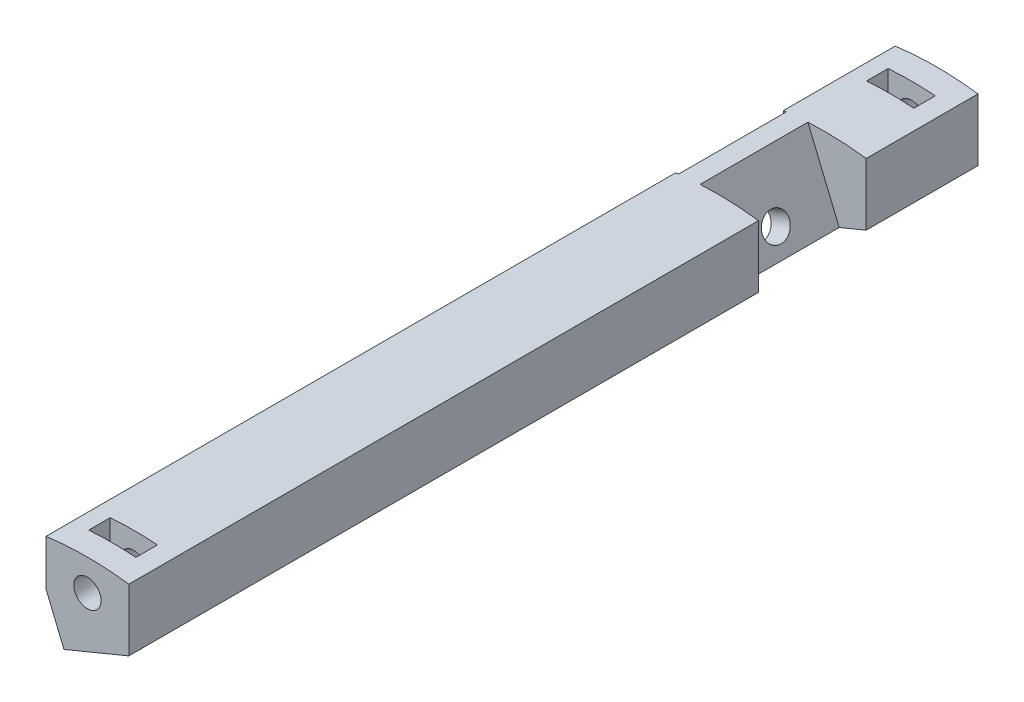
SolidWorks part; units mm, degrees
ref_plane "Plan de face" through (0, 0, 0) normal (0, 0, 1) x (1, 0, 0)
ref_plane "Plan de dessus" through (0, 0, 0) normal (0, 1, 0) x (1, 0, 0)
ref_plane "Plan de droite" through (0, 0, 0) normal (1, 0, 0) x (0, 0, -1)
sketch "Esquisse3" plane through (0, 0, 0) normal (0, 0, 1) x (1, 0, 0)
  line L3 (-5, 37.1652) -> (5, 37.1652) construction
  line L4 (-5, 37.1652) -> (-5, 0) construction
  line L5 (-5, 0) -> (5, 0) construction
  line L6 (5, 37.1652) -> (5, 0) construction
  line L7 (8.9994, 41.4168) -> (9.1038, 41.3823)
  line L8 (0, 0) -> (0, 37.5) construction
  line L9 (0, 0) -> (-14.3506, 34.6455) construction
  line L21 (15.6441, 34.081) -> (35.1609, -13.0369) construction
  line L30 (15.6441, 34.081) -> (-2.8335, 26.4273) construction
  line L31 (35.1609, -13.0369) -> (16.6833, -20.6905) construction
  line L32 (-2.8335, 26.4273) -> (16.6833, -20.6905) construction
  line L33 (-2.8335, 26.4273) -> (-10.4872, 44.9049) construction
  line L34 (-2.8335, 26.4273) -> (-0.9858, 27.1927) construction
  line L35 (-10.4872, 44.9049) -> (-8.6394, 45.6703) construction
  line L36 (-0.9858, 27.1927) -> (-8.6394, 45.6703) construction
  line L38 (5, 29.6657) -> (-2.8335, 26.4273)
  line L39 (-2.8335, 26.4273) -> (-5, 31.6576)
  line L40 (-5, 31.6576) -> (-5, 37.1652)
  line L41 (5, 37.1652) -> (5, 29.6657)
  circle A0 centre (0, 0) radius 37.5 construction
  circle A1 centre (0, 0) radius 30 construction
  arc A2 (-5, 37.1652) -> (5, 37.1652) centre (0, 0) cw
  point P5 (0, 0)
  dimension "D1" = 75
  dimension "D2" = 60
  dimension "D4" = 22.5
  dimension "D5" = 51
  dimension "D3" = 10
  dimension "D6" = 20
  dimension "D7" = 20
  dimension "D8" = 2
extrude "Boss.-Extru.2" add sketch "Esquisse3" along normal blind 102.5
sketch "Esquisse8" plane through (0, 0, 0) normal (0, 0, -1) x (-1, 0, 0)
  line L0 (-30, 0) -> (-37.5, 0) construction
  circle A0 centre (0, 0) radius 33.75 construction
  circle A1 centre (0, 33.75) radius 1.75
  circle A2 centre (0, 0) radius 37.5 construction
  circle A3 centre (0, 0) radius 30 construction
  point P10 (-33.75, 0)
  dimension "D2" = 3.5
  dimension "D3" = 60
extrude "Enlèv. mat.-Extru.5" cut sketch "Esquisse8" against normal blind 11.5
sketch "Esquisse9" plane through (0, 0, 0) normal (0, 0, -1) x (-1, 0, 0)
  line L0 (-2.85, 37.3915) -> (-2.85, 31.9954)
  line L1 (-2.85, 31.9954) -> (0, 30.35)
  line L2 (0, 30.35) -> (2.85, 31.9954)
  line L3 (2.85, 31.9954) -> (2.85, 37.3915)
  line L4 (-2.85, 31.9954) -> (2.85, 31.9954) construction
  arc A0 (5, 37.1652) -> (-5, 37.1652) centre (0, 0) ccw construction
  arc A1 (2.85, 37.3915) -> (-2.85, 37.3915) centre (0, 0) ccw
  circle A2 centre (0, 33.75) radius 1.75 construction
  point P9 (0, 31.9954)
  dimension "D3" = 3.4
  dimension "D1" = 120
  dimension "D2" = 5.7
extrude "Enlèv. mat.-Extru.6" cut sketch "Esquisse9" against normal blind 2.6 from offset 3 offset against normal yes
sketch "Esquisse14" plane through (0, 0, 102.5) normal (0, 0, 1) x (1, 0, 0)
  line L13 (16.2561, 33.7933) -> (35.3903, -12.4007) construction
  line L15 (35.3903, -12.4007) -> (16.9127, -20.0543) construction
  line L16 (-2.2215, 26.1396) -> (16.9127, -20.0543) construction
  line L17 (0, 0) -> (-37.5, 0) construction
  line L18 (0, 0) -> (-14.3506, 34.6455) construction
  line L26 (16.2561, 33.7933) -> (-2.2215, 26.1396) construction
  line L27 (-2.2215, 26.1396) -> (-9.8751, 44.6172) construction
  line L28 (-9.8751, 44.6172) -> (-8.0274, 45.3826) construction
  line L29 (-8.0274, 45.3826) -> (-0.3737, 26.905) construction
  line L36 (-0.5644, 27.3654) -> (1.7458, 28.3209)
  line L37 (5, 29.6657) -> (-2.8335, 26.4273) construction
  line L38 (1.7458, 28.3209) -> (-2.0335, 37.4448)
  line L40 (-0.5644, 27.3654) -> (-4.6428, 37.2115)
  circle A0 centre (0, 0) radius 37.5 construction
  arc A1 (5, 37.1652) -> (-5, 37.1652) centre (0, 0) ccw construction
  arc A3 (-2.0335, 37.4448) -> (-4.6428, 37.2115) centre (0, 0) ccw
  dimension "D1" = 2
  dimension "D2" = 20
  dimension "D3" = 67.5
  dimension "D4" = 2.5
  dimension "D6" = 50
  dimension "D7" = 20
extrude "Enlèv. mat.-Extru.11" cut sketch "Esquisse14" against normal blind 13 from offset 76 offset against normal yes
sketch "Esquisse15" plane through (11.5031, 4.7647, 0) normal (0.9239, 0.3827, 0) x (0, 0, -1)
  line L0 (-13.5, 25.4965) -> (-102.5, 25.4965) construction
  line L2 (-20, 28.4965) -> (-13.5, 28.4965) construction
  line L3 (-13.5, 25.497) -> (-13.5, 35.3727) construction
  line L4 (-20, 28.4965) -> (-26.5, 28.4965) construction
  line L5 (-26.5, 25.497) -> (-26.5, 35.3727) construction
  circle A0 centre (-20, 28.4965) radius 1.625
  dimension "D1" = 3.25
  dimension "D3" = 3
extrude "Enlèv. mat.-Extru.12" cut sketch "Esquisse15" against normal through all
chamfer "Chanfrein1" distance 2.5 angle 45 2 edges at (-1.699, 26.8963, 13.5) (-1.699, 26.8963, 26.5)
sketch "Esquisse16" plane through (0, 0, 102.5) normal (0, 0, 1) x (1, 0, 0)
  line L0 (-37.5, 0) -> (-30, 0) construction
  circle A0 centre (0, 0) radius 37.5 construction
  circle A1 centre (0, 0) radius 30 construction
  arc A2 (5, 37.1652) -> (-5, 37.1652) centre (0, 0) ccw construction
  circle A3 centre (0, 0) radius 33.75 construction
  circle A4 centre (0, 33.75) radius 1.65
  point P10 (-33.75, 0)
  dimension "D1" = 60
  dimension "D2" = 3.3
extrude "Enlèv. mat.-Extru.13" cut sketch "Esquisse16" against normal blind 11.5
sketch "Esquisse17" plane through (0, 0, 102.5) normal (0, 0, 1) x (1, 0, 0)
  line L0 (-2.85, 37.3915) -> (-2.85, 31.9954)
  line L1 (-2.85, 31.9954) -> (0, 30.35)
  line L2 (0, 30.35) -> (2.85, 31.9954)
  line L3 (2.85, 31.9954) -> (2.85, 37.3915)
  line L4 (-2.85, 31.9954) -> (2.85, 31.9954) construction
  arc A1 (2.85, 37.3915) -> (-2.85, 37.3915) centre (0, 0) ccw
  point P9 (0, 31.9954)
  dimension "D1" = 120
  dimension "D2" = 5.7
extrude "Enlèv. mat.-Extru.14" cut sketch "Esquisse17" against normal blind 2.6 from offset 3 offset against normal yes
